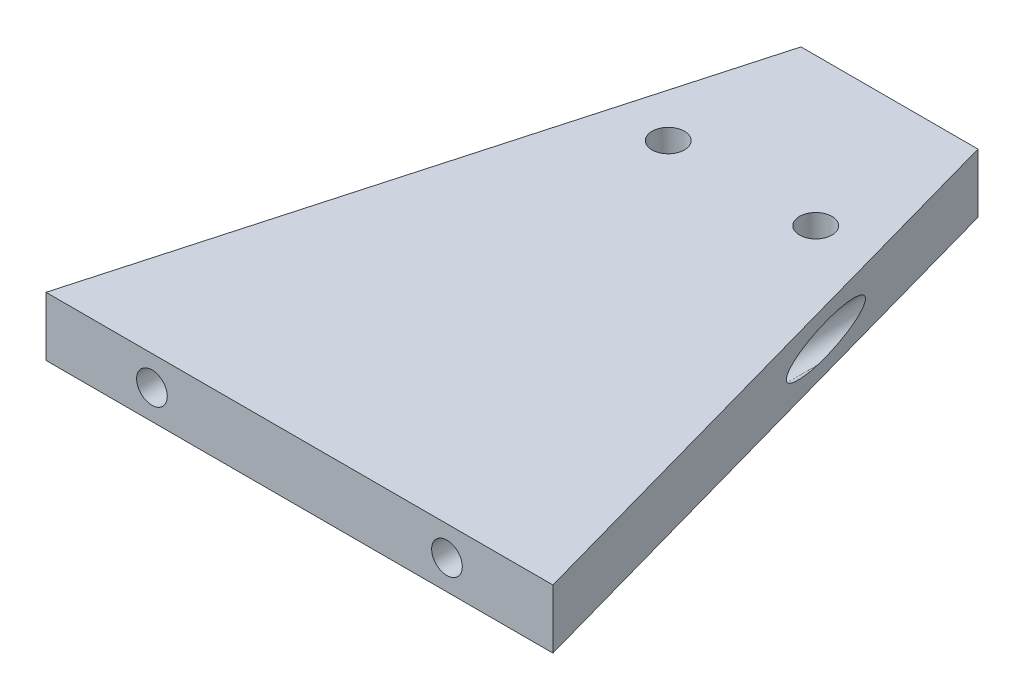
SolidWorks part; units mm, degrees
material "ABS"
ref_plane "Front Plane" through (0, 0, 0) normal (0, 0, 1) x (1, 0, 0)
ref_plane "Top Plane" through (0, 0, 0) normal (0, 1, 0) x (1, 0, 0)
ref_plane "Right Plane" through (0, 0, 0) normal (1, 0, 0) x (0, 0, -1)
sketch "Sketch1" plane through (0, 0, 0) normal (0, 1, 0) x (1, 0, 0)
  line L0 (0, 127) -> (63.5, 127)
  line L1 (63.5, 127) -> (63.5, 0)
  line L2 (63.5, 0) -> (-63.5, 0)
  line L3 (-63.5, 0) -> (-63.5, 127)
  line L4 (-63.5, 127) -> (0, 127)
  line L5 (-63.5, 95.25) -> (-15.875, 95.25) construction
  line L6 (-15.875, 95.25) -> (15.875, 95.25) construction
  line L7 (15.875, 95.25) -> (63.5, 95.25) construction
  circle A0 centre (-15.875, 95.25) radius 3.4925
  circle A1 centre (15.875, 95.25) radius 3.4925
  dimension "D3" = 6.985
  dimension "D1" = 127
  dimension "D2" = 31.75
  dimension "D4" = 31.75
  dimension "D5" = 127
extrude "Boss-Extrude1" add sketch "Sketch1" along normal blind 12.7
sketch "Sketch3" plane through (0, 0, 0) normal (0, 0, 1) x (1, 0, 0)
  line L0 (-78.7739, 6.35) -> (79.2116, 6.35) construction
  line L1 (-63.5, 12.7) -> (-63.5, 0) construction
  line L2 (63.5, 12.7) -> (63.5, 0) construction
  circle A0 centre (-31.75, 6.35) radius 3.302
  circle A1 centre (31.75, 6.35) radius 3.302
  point P12 (-63.5, 6.35)
  dimension "D1" = 6.604
  dimension "D2" = 31.75
  dimension "D3" = 31.75
extrude "Cut-Extrude1" cut sketch "Sketch3" against normal through all
sketch "Sketch4" plane through (0, 12.7, 0) normal (0, 1, 0) x (1, 0, 0)
  line L0 (-63.5, -32.004) -> (63.5, -32.004) construction
  line L1 (-63.5, 127) -> (-63.5, 0) construction
  line L2 (63.5, 0) -> (63.5, 127) construction
  line L3 (63.5, 127) -> (-63.5, 127) construction
  line L4 (0, 127) -> (19.05, 127) construction
  line L5 (0, 127) -> (-19.05, 127) construction
  line L6 (-63.5, -32.004) -> (-19.05, 127)
  line L7 (19.05, 127) -> (63.5, -32.004)
  line L8 (-63.5, -32.004) -> (-63.5, 127)
  line L9 (-63.5, 127) -> (-19.05, 127)
  line L10 (19.05, 127) -> (63.5, 127)
  line L11 (63.5, 127) -> (63.5, -32.004)
  dimension "D1" = 159.004
  dimension "D2" = 38.1
extrude "Cut-Extrude2" cut sketch "Sketch4" against normal through all
